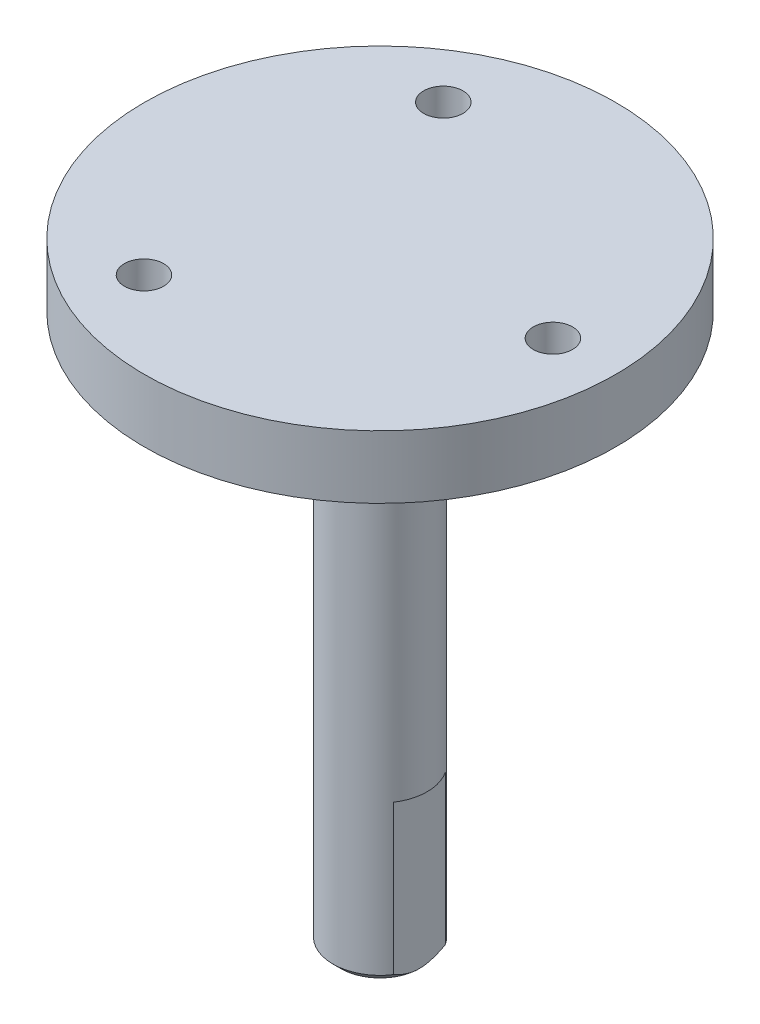
SolidWorks part; units mm, degrees
ref_plane "Alzado" through (0, 0, 0) normal (0, 0, 1) x (1, 0, 0)
ref_plane "Planta" through (0, 0, 0) normal (0, 1, 0) x (1, 0, 0)
ref_plane "Vista lateral" through (0, 0, 0) normal (1, 0, 0) x (0, 0, -1)
sketch "Croquis1" plane through (0, 0, 0) normal (0, 0, 1) x (1, 0, 0)
  line L0 (0, 0) -> (3, 0)
  line L5 (3, 0) -> (3, -39)
  line L6 (3, -39) -> (0, -39)
  line L7 (0, -39) -> (0, 0)
  line L8 (0, -39) -> (0, 5.7552) construction
  dimension "D3" = 39
  dimension "D7" = 6
revolve "Revolución1" add sketch "Croquis1" angle 360 about L8 region at (1.5, -19.5, 0)
sketch "Croquis2" plane through (0, -39, 0) normal (0, -1, 0) x (1, 0, 0)
  line L0 (2.5, 1.6583) -> (2.5, -1.6583)
  line L1 (0, 0) -> (3, 0) construction
  circle A0 centre (0, 0) radius 3
  circle A1 centre (0, 0) radius 3
  circle M3 centre (0, 0) radius 3
  dimension "D1" = 0.5
extrude "Cortar-Extruir1" cut sketch "Croquis2" against normal blind 10 contours L1 L0 M3 | L0 L1 A1 region at (2.7015, -39, 0.6294) region at (2.7015, -39, -0.6294)
sketch "Croquis4" plane through (0, 0, 0) normal (0, 1, 0) x (1, 0, 0)
  circle A2 centre (0, 0) radius 15
  dimension "D1" = 30
extrude "Saliente-Extruir1" add sketch "Croquis4" against normal blind 4
sketch "Croquis5" plane through (0, 0, 0) normal (0, 1, 0) x (1, 0, 0)
  line L0 (0, 0) -> (11, 0) construction
  point P0 (11, 0)
  point P5 (-5.5, -9.5263)
  point P8 (-5.5, 9.5263)
  dimension "D1" = 11
  dimension "D2" = 3
hole_wizard "Perforador para roscar para macho de roscar para M3x0.51" positions "Croquis5" profile "Croquis6" hole size "M3x0.5" standard "Ansi Metric" end condition up to next
sketch "Croquis6" plane through (11, 0, 0) normal (1, 0, 0) x (0, 0, 1)
  line L0 (0, 0) -> (0, 4)
  line L1 (0, 4) -> (1.25, 4)
  line L2 (1.25, 4) -> (1.25, 0)
  line L5 (1.25, 0) -> (0, 0)
  line L11 (0, -6.35) -> (0, 107.95) construction
  dimension "Diámetro de taladro hasta el siguiente" = 2.5
  dimension "Profundidad de taladro hasta el siguiente" = 4
cosmetic thread "Rosca cosmética1" parameters "D2"=3
cosmetic thread "Rosca cosmética2" parameters "D2"=3
cosmetic thread "Rosca cosmética3" parameters "D2"=3
cosmetic thread "Rosca cosmética4" parameters "D2"=3
chamfer "Chaflán1" distance 0.5 angle 45 1 edges at (-3, -39, 0)
equation "\"ParaTuerca\"= 20mm"
equation "\"gap\"= 2mm"
equation "\"ParMotor\"= 20mm"
equation "\"D1@Cortar-Extruir1\"=\"ParMotor\"-10"
